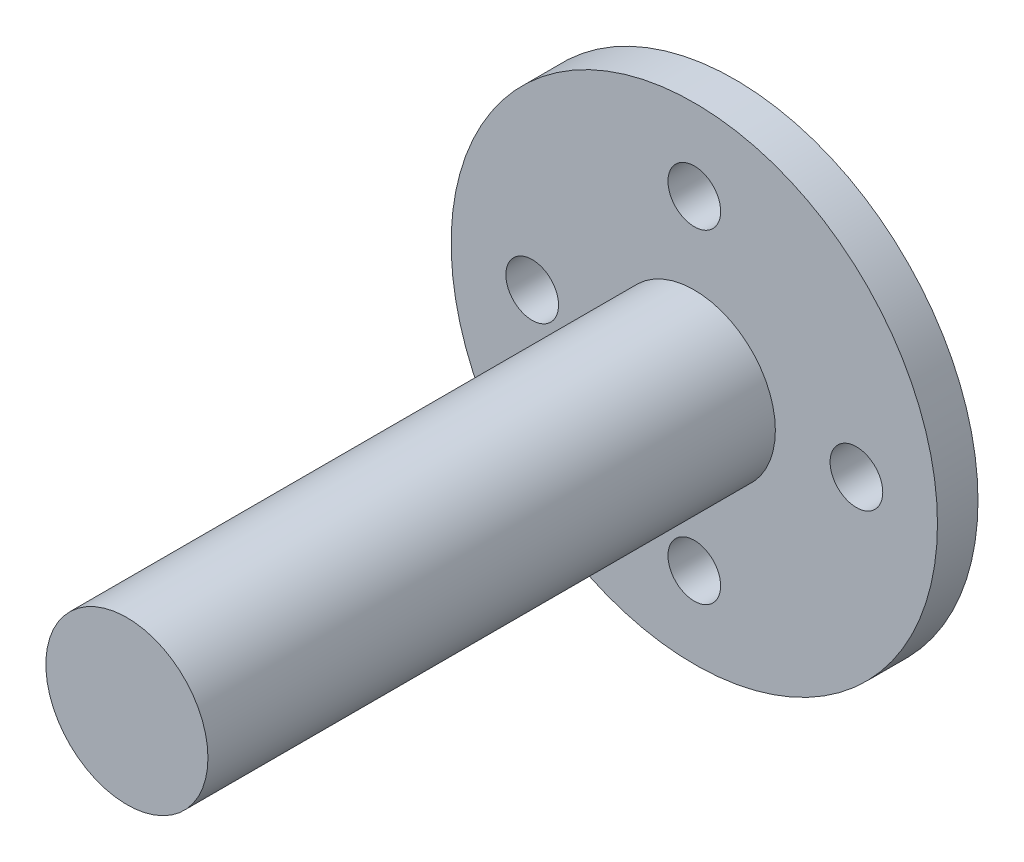
SolidWorks part; units mm, degrees
material "AISI 304"
ref_plane "Front Plane" through (0, 0, 0) normal (0, 0, 1) x (1, 0, 0)
ref_plane "Top Plane" through (0, 0, 0) normal (0, 1, 0) x (1, 0, 0)
ref_plane "Right Plane" through (0, 0, 0) normal (1, 0, 0) x (0, 0, -1)
sketch "Hub_Flange_Profile" plane through (0, 0, 0) normal (0, 0, 1) x (1, 0, 0)
  circle A0 centre (0, 0) radius 30
  circle A1 centre (20, 0) radius 3.25
  circle A2 centre (0, 20) radius 3.25
  circle A3 centre (-20, 0) radius 3.25
  circle A4 centre (0, -20) radius 3.25
  dimension "Hub_Diameter" = 60
  dimension "Bolt_Hole_Diameter" = 6.5
  dimension "Bolt_Radius" = 20
  dimension "Bolt_Radius_2" = 20
  dimension "Bolt_Radius_3" = 20
  dimension "Bolt_Radius_4" = 20
extrude "Hub_Flange_5mm" add sketch "Hub_Flange_Profile" along normal blind 5
sketch "Stub_Axle_Profile" plane through (0, 0, 0) normal (0, 0, 1) x (1, 0, 0)
  circle A0 centre (0, 0) radius 10
  dimension "Shaft_Diameter" = 20
extrude "Stub_Axle_75mm" add sketch "Stub_Axle_Profile" along normal blind 75
ref_axis "Stub_Axis" through (0, 0, -3.75) along (0, 0, 1)
ref_plane "Stub_End_Plane" through (0, 0, 75) normal (0, 0, 1) x (1, 0, 0)
